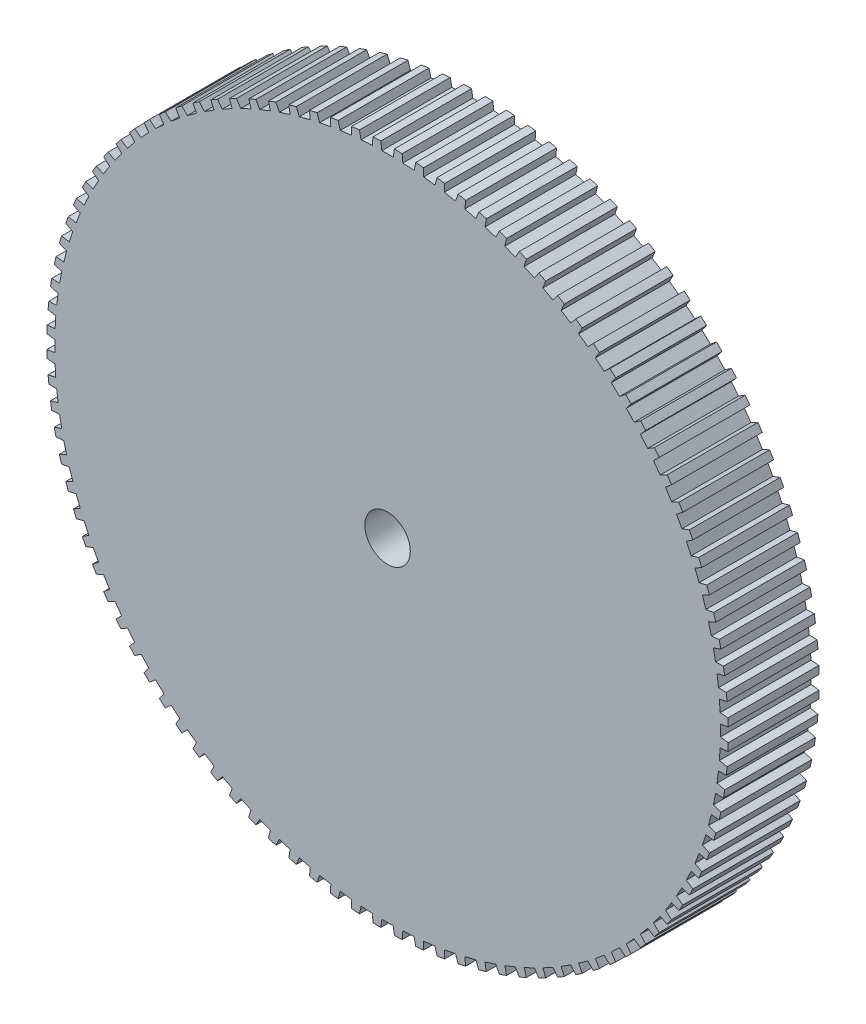
SolidWorks part; units mm, degrees
ref_plane "Front Plane" through (0, 0, 0) normal (0, 0, 1) x (1, 0, 0)
ref_plane "Top Plane" through (0, 0, 0) normal (0, 1, 0) x (1, 0, 0)
ref_plane "Right Plane" through (0, 0, 0) normal (1, 0, 0) x (0, 0, -1)
sketch "Sketch1" plane through (0, 0, 0) normal (0, 0, 1) x (1, 0, 0)
  circle A0 centre (0, 0) radius 33 construction
  circle A2 centre (0, 0) radius 30
  dimension "D1" = 66
  dimension "rubberthk" = 3
extrude "Boss-Extrude1" add sketch "Sketch1" along normal blind 8
sketch "Sketch4" plane through (0, 0, 0) normal (0, 0, -1) x (-1, 0, 0)
  circle A0 centre (0, 0) radius 4.85
  dimension "D1" = 9.7
extrude "Boss-Extrude2" add sketch "Sketch4" along normal blind 8
sketch "Sketch2" plane through (0, 0, 8) normal (0, 0, 1) x (1, 0, 0)
  circle A0 centre (0, 0) radius 4
  dimension "D1" = 8
extrude "Cut-Extrude1" cut sketch "Sketch2" against normal blind 4.35
sketch "Sketch5" plane through (0, 0, 3.65) normal (0, 0, 1) x (1, 0, 0)
  circle A0 centre (0, 0) radius 2
  dimension "D1" = 4
extrude "Cut-Extrude2" cut sketch "Sketch5" against normal offset from surface (4.15 mm away) 7.5 up to face at (-4.85, 0, -8)
sketch "Sketch6" plane through (0, 0, -8) normal (0, 0, -1) x (-1, 0, 0)
  line L0 (2.0785, 1.95) -> (-2.0785, 1.95)
  line L1 (-2.0785, -1.95) -> (2.0785, -1.95)
  arc A0 (2.0785, -1.95) -> (2.0785, 1.95) centre (0, 0) ccw
  arc A1 (-2.0785, 1.95) -> (-2.0785, -1.95) centre (0, 0) ccw
  dimension "D2" = 5.7
  dimension "D1" = 3.9
extrude "Cut-Extrude3" cut sketch "Sketch6" against normal up to surface (7.5 mm away) up to face at (-2, 0, -0.5)
sketch "Sketch7" plane through (0, 0, 8) normal (0, 0, 1) x (1, 0, 0)
  line L0 (-0.6, 29.994) -> (-0.5, 29.31)
  line L1 (-0.5, 29.31) -> (0.5, 29.31)
  line L2 (0.5, 29.31) -> (0.6, 29.994)
  line L3 (0, 0) -> (-0.6, 29.994) construction
  line L4 (0, 0) -> (0.6, 29.994) construction
  circle A0 centre (0, 0) radius 30 construction
  arc A1 (0.6, 29.994) -> (-0.6, 29.994) centre (0, 0) ccw
  point P8 (0, 29.31)
  dimension "D1" = 1
  dimension "D2" = 1.2
  dimension "D3" = 0.69
extrude "Cut-Extrude4" cut sketch "Sketch7" against normal through all
pattern_circular "CirPattern1" count 100 over 360 about axis through (0, 0, 8) along (0, 0, -1) of "Cut-Extrude4"
sketch "Sketch8" plane through (0, 0, 3.65) normal (0, 0, 1) x (1, 0, 0)
  circle A0 centre (0, 0) radius 2 construction
  circle A1 centre (0, 0) radius 4
  circle A2 centre (0, 0) radius 4
  circle A3 centre (0, 0) radius 2
  dimension "D1" = 0
extrude "ReverseCountersink" add sketch "Sketch8" along normal up to surface (4.35 mm away) up to face at (0, 0, 8)
equation "\"width\"= 24"
equation "\"thk\"= 3"
equation "\"holesize\"= 4.2"
equation "\"holedistance\"= ( 20 + 12 ) / 2"
equation "\"threaded_hole\"= 3.9"
equation "\"fillet_radius\"= 2"
equation "\"ground_clearance\"= 25"
equation "\"tire_thk\"= 3"
equation "\"innerwheel_diam\" = \"wheel_diam\"-2*\"tire_thk\""
equation "\"innerwheel_thk\"= 8"
equation "\"wheel_diam\"= 2*(\"width\"/2+\"ground_clearance\")"
equation "\"rubberthk@Sketch1\"=\"tire_thk\""
equation "\"D1@Boss-Extrude1\"=\"innerwheel_thk\""
equation "\"coloursensor_holesize\"= 2.65"
equation "\"hole_to_edge\" = 4"
equation "\"D1@Sketch1\"=60 + 2 * \"tire_thk\""
